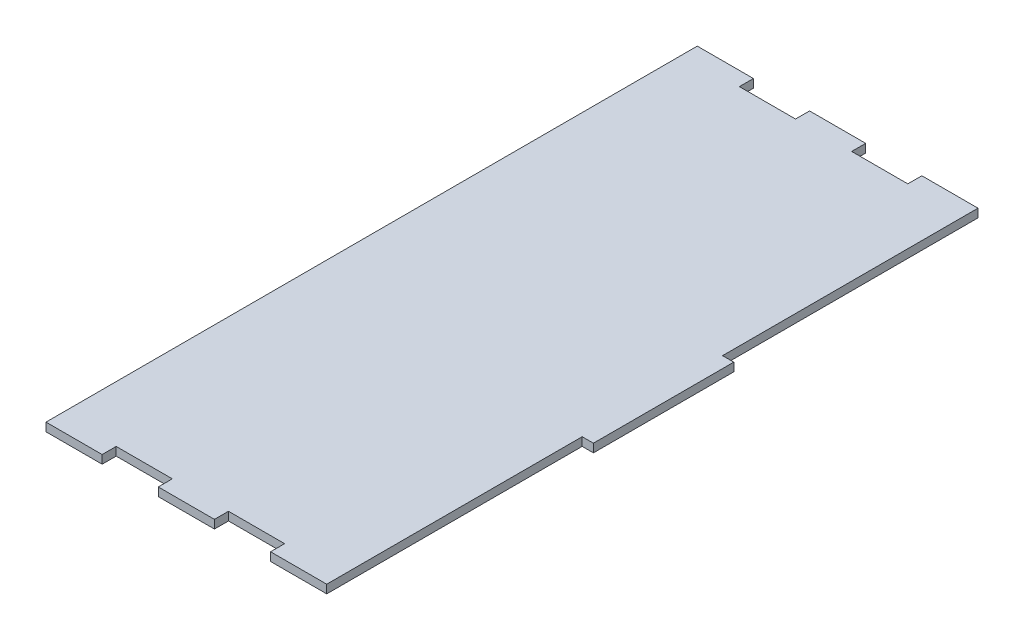
SolidWorks part; units mm, degrees
ref_plane "Front Plane" through (0, 0, 0) normal (0, 0, 1) x (1, 0, 0)
ref_plane "Top Plane" through (0, 0, 0) normal (0, 1, 0) x (1, 0, 0)
ref_plane "Right Plane" through (0, 0, 0) normal (1, 0, 0) x (0, 0, -1)
sketch "Sketch1" plane through (0, 0, 0) normal (0, 1, 0) x (1, 0, 0)
  line L0 (-50, -111) -> (-50, -116)
  line L1 (30, 111) -> (10, 111)
  line L2 (50, 111) -> (50, 25)
  line L3 (30, -111) -> (10, -111)
  line L4 (-50, 111) -> (-50, -111)
  line L5 (50, 111) -> (-50, -111) construction
  line L6 (50, -111) -> (-50, 111) construction
  line L7 (-50, -116) -> (-30, -116)
  line L8 (-30, -116) -> (-30, -111)
  line L9 (-10, -111) -> (-10, -116)
  line L10 (-10, -116) -> (10, -116)
  line L11 (10, -116) -> (10, -111)
  line L12 (30, -111) -> (30, -116)
  line L13 (30, -116) -> (50, -116)
  line L14 (50, -116) -> (50, -111)
  line L15 (-50, 0) -> (50, 0) construction
  line L16 (0, -116) -> (0, 116) construction
  line L17 (50, 116) -> (50, 111)
  line L18 (30, 116) -> (50, 116)
  line L19 (30, 111) -> (30, 116)
  line L20 (10, 116) -> (10, 111)
  line L21 (-10, 116) -> (10, 116)
  line L22 (-10, 111) -> (-10, 116)
  line L23 (-30, 116) -> (-30, 111)
  line L24 (-50, 116) -> (-30, 116)
  line L25 (-50, 111) -> (-50, 116)
  line L26 (-10, 111) -> (-30, 111)
  line L27 (-10, -111) -> (-30, -111)
  line L28 (50, -25) -> (50, -111)
  line L29 (50, -25) -> (54, -25)
  line L31 (50, 25) -> (54, 25)
  line L32 (54, -25) -> (54, 25)
  point P0 (0, 0)
  dimension "D1" = 100
  dimension "D2" = 222
  dimension "D3" = 5
  dimension "D4" = 20
  dimension "D6" = 50
  dimension "D7" = 4
  dimension "D5" = 3
extrude "Boss-Extrude1" add sketch "Sketch1" along normal blind 3
